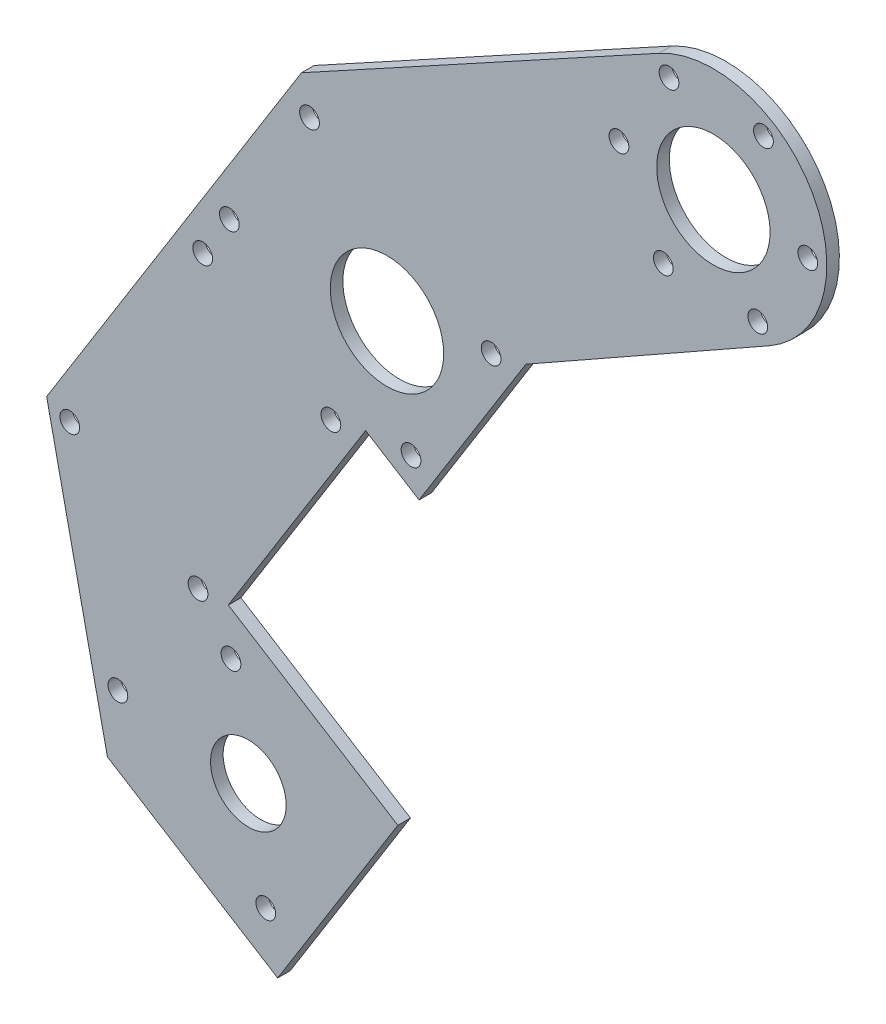
SolidWorks part; units mm, degrees
ref_plane "Front Plane" through (0, 0, 0) normal (0, 0, 1) x (1, 0, 0)
ref_plane "Top Plane" through (0, 0, 0) normal (0, 1, 0) x (1, 0, 0)
ref_plane "Right Plane" through (0, 0, 0) normal (1, 0, 0) x (0, 0, -1)
sketch "Sketch1" plane through (0, 0, -14.1946) normal (0, 0, 1) x (1, 0, 0)
  line L0 (-11.4036, 461.0409) -> (18.8813, 509.5069)
  line L1 (-54.3079, 487.8505) -> (-69.6155, 558.824)
  line L2 (18.8813, 509.5069) -> (-23.8465, 536.2061)
  line L3 (10.7592, 591.5868) -> (-157.4902, 322.3315) construction
  line L4 (-11.4036, 461.0409) -> (-54.3079, 487.8505)
  line L5 (-69.6155, 558.824) -> (-5.4017, 661.5875)
  line L6 (-23.8465, 536.2061) -> (10.7592, 591.5868)
  line L8 (-115.7964, 730.5698) -> (51.1419, 626.2552) construction
  line L9 (-142.7163, 687.4889) -> (24.222, 583.1743) construction
  line L10 (51.1419, 626.2552) -> (112.462, 660.9373)
  line L11 (10.7592, 591.5868) -> (24.222, 583.1743)
  line L13 (24.222, 583.1743) -> (51.1419, 626.2552)
  line L16 (-5.4017, 661.5875) -> (84.678, 710.8773)
  line L17 (16.1415, 618.1747) -> (-107.7159, 695.5694) construction
  line L18 (3.7388, 485.2739) -> (-32.2498, 508.4981) construction
  circle A2 centre (16.1415, 618.1747) radius 14.2875
  circle A3 centre (-18.7876, 499.8107) radius 9.525
  circle A5 centre (98.3945, 685.8096) radius 14.2875
  arc A7 (112.462, 660.9373) -> (84.678, 710.8773) centre (98.3945, 685.8096) ccw
  circle A8 centre (-107.7159, 695.5694) radius 215.011 construction
  point P31 (-19.9236, 500.5437)
  point P32 (-19.9236, 500.5437)
  point P33 (98.3945, 685.8096)
  point P34 (-18.7876, 499.8107)
extrude "Boss-Extrude1" add sketch "Sketch1" along normal blind 3.175
sketch "Sketch17" plane through (0, 0, -11.0196) normal (0, 0, 1) x (1, 0, 0)
  line L0 (-14.4068, 474.7913) -> (-18.7876, 499.8107) construction
  line L1 (-18.7876, 499.8107) -> (-23.1685, 524.83) construction
  line L2 (16.1415, 618.1747) -> (37.6819, 604.7147) construction
  line L12 (24.222, 583.1743) -> (51.1419, 626.2552) construction
  line L13 (37.6819, 604.7147) -> (27.587, 588.5594) construction
  line L14 (27.587, 588.5594) -> (22.2019, 591.9244) construction
  line L15 (22.2019, 591.9244) -> (-28.9566, 623.8918) construction
  line L16 (-5.4017, 661.5875) -> (-69.6155, 558.824) construction
  line L17 (-28.9566, 623.8918) -> (-23.5715, 620.5268) construction
  line L18 (-23.5715, 620.5268) -> (-3.3816, 652.8374) construction
  line L19 (-3.3816, 652.8374) -> (42.3918, 624.2351) construction
  line L20 (10.7592, 591.5868) -> (5.3741, 594.9518) construction
  line L21 (5.3741, 594.9518) -> (-31.4748, 535.9811) construction
  line L22 (-31.4748, 535.9811) -> (-51.6648, 503.6705) construction
  line L23 (5.3741, 594.9518) -> (2.0091, 589.5667) construction
  line L24 (-31.4748, 535.9811) -> (-63.7855, 556.1711) construction
  line L25 (2.0091, 589.5667) -> (-30.3015, 609.7566) construction
  circle A0 centre (-18.7876, 499.8107) radius 25.4
  point P16 (-19.9236, 500.5437)
  point P30 (-18.7876, 499.8107)
hole_wizard "#10 Clearance Hole2" positions "Sketch20" profile "Sketch21" hole size "#10" standard "ANSI Inch" end condition through all
sketch "Sketch20" plane through (0, 0, -11.0196) normal (0, 0, 1) x (1, 0, 0)
  point P0 (-23.1685, 524.83)
  point P3 (-14.4068, 474.7913)
  point P24 (-3.3816, 652.8374)
  point P27 (42.3918, 624.2351)
  point P30 (22.2019, 591.9244)
  point P33 (-23.5715, 620.5268)
  point P42 (-31.4748, 535.9811)
  point P45 (-63.7855, 556.1711)
  point P48 (-51.6648, 503.6705)
  point P54 (2.0091, 589.5667)
  point P57 (-30.3015, 609.7566)
sketch "Sketch21" plane through (-23.1685, 524.83, -11.0196) normal (1, 0, 0) x (0, -1, 0)
  line L0 (0, 0) -> (0, 3.175)
  line L1 (0, 3.175) -> (2.4892, 3.175)
  line L2 (2.4892, 3.175) -> (2.4892, 0)
  line L5 (2.4892, 0) -> (0, 0)
  line L11 (0, -6.35) -> (0, 107.95) construction
  dimension "Thru Hole Dia." = 4.9784
  dimension "Thru Hole Depth" = 3.175
sketch "Sketch22" plane through (0, 0, -11.0196) normal (0, 0, 1) x (1, 0, 0)
  line L0 (98.3945, 685.8096) -> (111.0132, 706.0038) construction
  line L2 (111.0132, 706.0038) -> (87.2152, 706.8348) construction
  line L3 (87.2152, 706.8348) -> (74.5965, 686.6407) construction
  line L4 (74.5965, 686.6407) -> (85.7758, 665.6155) construction
  line L5 (85.7758, 665.6155) -> (109.5738, 664.7845) construction
  line L6 (109.5738, 664.7845) -> (122.1925, 684.9786) construction
  line L7 (122.1925, 684.9786) -> (111.0132, 706.0038) construction
  circle A0 centre (98.3945, 685.8096) radius 23.8125 construction
hole_wizard "#10 Clearance Hole3" positions "Sketch23" profile "Sketch24" hole size "#10" standard "ANSI Inch" end condition through all
sketch "Sketch23" plane through (0, 0, -11.0196) normal (0, 0, 1) x (1, 0, 0)
  point P0 (111.0132, 706.0038)
  point P3 (122.1925, 684.9786)
  point P6 (109.5738, 664.7845)
  point P9 (85.7758, 665.6155)
  point P12 (74.5965, 686.6407)
  point P15 (87.2152, 706.8348)
sketch "Sketch24" plane through (111.0132, 706.0038, -11.0196) normal (1, 0, 0) x (0, -1, 0)
  line L0 (0, 0) -> (0, 3.175)
  line L1 (0, 3.175) -> (2.4892, 3.175)
  line L2 (2.4892, 3.175) -> (2.4892, 0)
  line L5 (2.4892, 0) -> (0, 0)
  line L11 (0, -6.35) -> (0, 107.95) construction
  dimension "Thru Hole Dia." = 4.9784
  dimension "Thru Hole Depth" = 3.175
